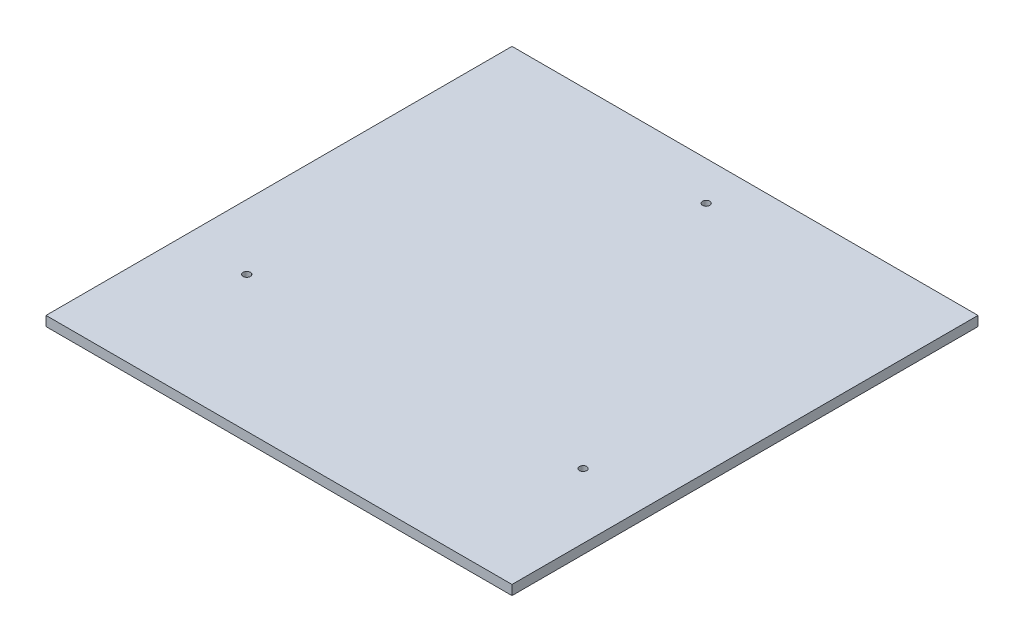
SolidWorks part; units mm, degrees
ref_plane "Front Plane" through (0, 0, 0) normal (0, 0, 1) x (1, 0, 0)
ref_plane "Top Plane" through (0, 0, 0) normal (0, 1, 0) x (1, 0, 0)
ref_plane "Right Plane" through (0, 0, 0) normal (1, 0, 0) x (0, 0, -1)
sketch "Sketch1" plane through (0, 0, 0) normal (0, 1, 0) x (1, 0, 0)
  line L1 (0, 0) -> (304.8, 0)
  line L2 (0, 0) -> (0, 304.8)
  line L3 (0, 304.8) -> (304.8, 304.8)
  line L4 (304.8, 0) -> (304.8, 304.8)
  dimension "D1" = 304.8
  dimension "D2" = 304.8
extrude "Boss-Extrude1" add sketch "Sketch1" along normal blind 6.35 contours L2 L3 L4 L1
sketch "Sketch2" plane through (0, 6.35, 0) normal (0, 1, 0) x (1, 0, 0)
  line L0 (0, 152.4) -> (304.8, 152.4) construction
  line L1 (0, 0) -> (0, 304.8) construction
  line L2 (304.8, 0) -> (304.8, 304.8) construction
  line L3 (152.4, 304.8) -> (152.4, 0) construction
  line L4 (0, 304.8) -> (304.8, 304.8) construction
  line L5 (0, 0) -> (304.8, 0) construction
  circle A0 centre (152.4, 279.4) radius 2.3813
  point P14 (0, 0)
  dimension "D1" = 4.7625
  dimension "D2" = 127
extrude "Cut-Extrude1" cut sketch "Sketch2" against normal blind 6.35
ref_plane "Plane1" through (152.4, 0, 0) normal (-1, 0, 0) x (0, 0, 1)
ref_plane "Plane2" through (0, 0, -152.4) normal (0, 0, 1) x (1, 0, 0)
ref_axis "Axis1" through (152.4, -0.3175, -152.4) along (0, 1, 0)
pattern_circular "CirPattern1" count 3 over 360 about axis through (152.4, -0.3175, -152.4) along (0, 1, 0) of "Cut-Extrude1"
